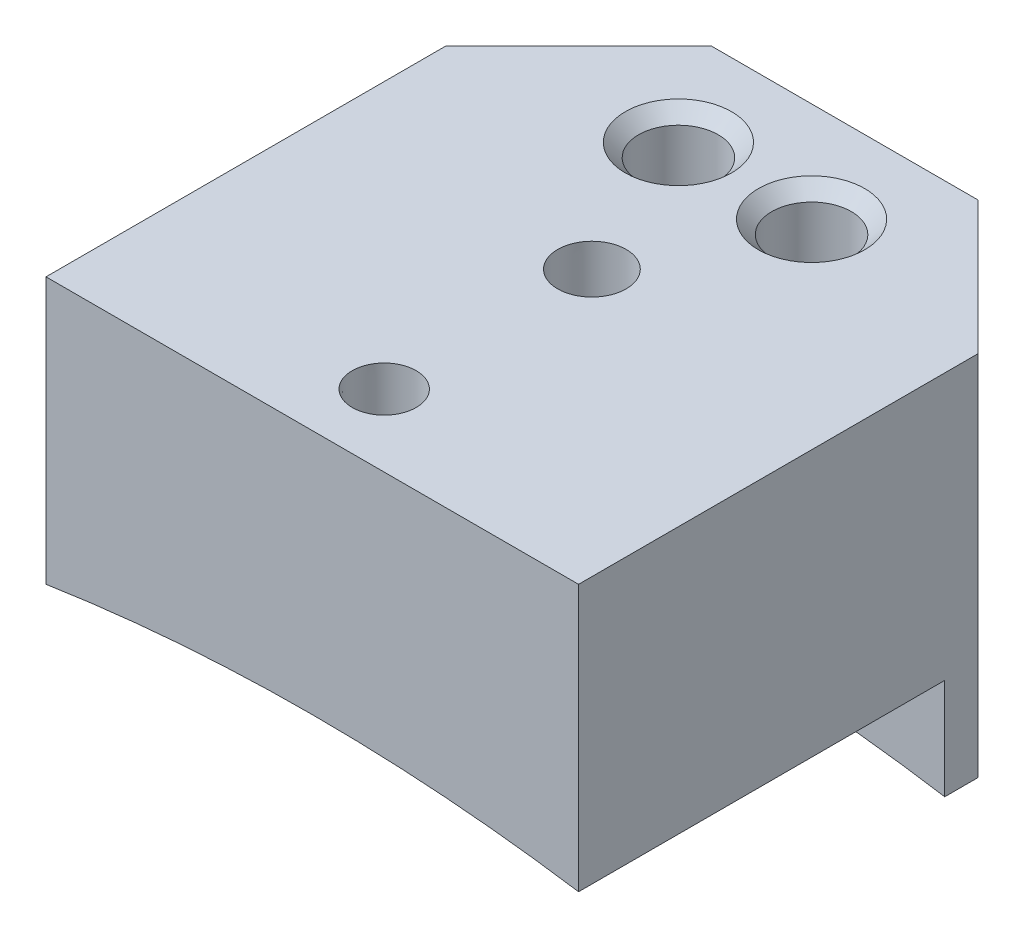
SolidWorks part; units mm, degrees
ref_plane "Front Plane" through (0, 0, 0) normal (0, 0, 1) x (1, 0, 0)
ref_plane "Top Plane" through (0, 0, 0) normal (0, 1, 0) x (1, 0, 0)
ref_plane "Right Plane" through (0, 0, 0) normal (1, 0, 0) x (0, 0, -1)
sketch "Sketch1" plane through (0, 0, 0) normal (0, 1, 0) x (1, 0, 0)
  line L0 (-28.5118, 6.4953) -> (-22.1618, 12.8453)
  line L1 (-22.1618, 12.8453) -> (-9.4618, 12.8453)
  line L2 (-28.5118, 6.4953) -> (-28.5118, -12.5547)
  line L3 (-28.5118, -12.5547) -> (-3.1118, -12.5547)
  line L4 (-3.1118, 6.4953) -> (-3.1118, -12.5547)
  line L5 (-9.4618, 12.8453) -> (-3.1118, 6.4953)
  line L6 (-15.8118, -12.5547) -> (-15.8118, 12.8453) construction
  line L8 (-3.1118, 6.4953) -> (-3.1118, 12.8453) construction
  line L9 (-3.1118, 12.8453) -> (-9.4618, 12.8453) construction
  dimension "D1" = 12.7
  dimension "D2" = 25.4
  dimension "D3" = 25.4
extrude "Boss-Extrude1" add sketch "Sketch1" along normal blind 12.7
sketch "Sketch2" plane through (0, 0, 12.5547) normal (0, 0, 1) x (1, 0, 0)
  circle A0 centre (-15.8118, -82.8523) radius 83.82
  dimension "D1" = 167.64
extrude "Cut-Extrude1" cut sketch "Sketch2" against normal through all both and the other way through all
sketch "Sketch5" plane through (0, 0, -12.8453) normal (0, 0, -1) x (-1, 0, 0)
  line L0 (3.1118, 12.7) -> (3.1118, 0) construction
  line L1 (3.1118, 12.7) -> (3.1118, 0)
  line L4 (28.5118, 12.7) -> (28.5118, 0) construction
  line L5 (28.5118, 12.7) -> (28.5118, 0)
  line L6 (28.5118, -4.8087) -> (28.5118, 0)
  line L7 (3.1118, -4.8087) -> (3.1118, 0)
  line L8 (3.1118, 12.7) -> (28.5118, 12.7)
  arc A0 (3.1118, -4.8087) -> (28.5118, -4.8087) centre (15.8118, -82.8523) cw
  arc A1 (28.5118, 0) -> (3.1118, 0) centre (15.8118, -82.8523) ccw construction
  arc A2 (28.5118, 0) -> (3.1118, 0) centre (15.8118, -82.8523) ccw construction
  dimension "D1" = 79.0702
extrude "Boss-Extrude2" add sketch "Sketch5" against normal blind 7.9375
chamfer "Chamfer1" distance 6.35 angle 45 2 edges at (-28.5118, 3.9457, -12.8453) (-3.1118, 3.9457, -12.8453)
hole_wizard "#10-24 Tapped Hole1" positions "Sketch3" profile "Sketch4" tap size "#10-24" standard "ANSI Inch" end condition through all
sketch "Sketch3" plane through (0, 12.7, 0) normal (0, 1, 0) x (1, 0, 0)
  line L0 (-15.8118, 12.8453) -> (-15.8118, 3.4006) construction
  line L1 (-9.4618, 12.8453) -> (-22.1618, 12.8453) construction
  point P0 (-18.9868, 8.0828)
  point P10 (0, 0)
  point P11 (0, 0)
  point P12 (-12.6368, 8.0828)
  dimension "D1" = 4.7625
  dimension "D2" = 3.175
sketch "Sketch4" plane through (-18.9868, 12.7, -8.0828) normal (1, 0, 0) x (0, 0, 1)
  line L0 (0, 0) -> (0, 17.5087)
  line L1 (0, 17.5087) -> (1.8986, 17.5087)
  line L2 (1.8986, 17.5087) -> (1.8986, 0.635)
  line L3 (1.8986, 0.635) -> (2.5337, 0)
  line L5 (2.5337, 0) -> (0, 0)
  line L6 (-1.8986, 0.635) -> (-2.5337, 0) construction
  line L11 (0, -6.35) -> (0, 107.95) construction
  dimension "Thru Tap Drill Dia." = 3.7973
  dimension "Thru Tap Drill Depth" = 17.5087
  dimension "Near C'Sink Dia." = 5.0673
  dimension "Near C'Sink Angle" = 90
cosmetic thread "Hole Thread3" parameters "D2"=4.826
cosmetic thread "Hole Thread4" parameters "D2"=4.826
sketch "Sketch6" plane through (0, 12.7, 0) normal (0, 1, 0) x (1, 0, 0)
  spline S0 degree 3 poles (-15.9109, -10.6497) (-15.6088, -10.6497) (-15.4088, -10.6093) (-15.0421, -10.4569) (-14.8723, -10.3433) (-14.6614, -10.1321) (-14.5971, -10.0536) (-14.4867, -9.888) (-14.44, -9.8004) (-14.3254, -9.523) (-14.286, -9.3252) (-14.2863, -9.0237) (-14.2962, -8.9248) (-14.3351, -8.7299) (-14.3646, -8.633) (-14.4412, -8.4488) (-14.488, -8.3613) (-14.5989, -8.1955) (-14.6633, -8.1172) (-14.8743, -7.9067) (-15.0444, -7.7932) (-15.4113, -7.6415) (-15.6118, -7.6017) (-15.9102, -7.6018) (-16.0112, -7.6118) (-16.2064, -7.6508) (-16.3014, -7.6796) (-16.5784, -7.7944) (-16.7462, -7.9063) (-16.9595, -8.1198) (-17.0224, -8.1968) (-17.1327, -8.362) (-17.1804, -8.4512) (-17.2567, -8.6357) (-17.2855, -8.7307) (-17.3244, -8.9262) (-17.3342, -9.0271) (-17.3341, -9.3253) (-17.2941, -9.5259) (-17.142, -9.8926) (-17.0285, -10.0627) (-16.8176, -10.2736) (-16.7392, -10.3379) (-16.5735, -10.4485) (-16.486, -10.4953) (-16.3014, -10.5718) (-16.2047, -10.6011) (-16.0099, -10.6398) (-15.9109, -10.6497) (-15.6088, -10.6497) (-15.4088, -10.6093) knots -0.03125 -0.03125 0 0 0.0625 0.0625 0.125 0.125 0.15625 0.15625 0.1875 0.1875 0.25 0.25 0.28125 0.28125 0.3125 0.3125 0.34375 0.34375 0.375 0.375 0.4375 0.4375 0.5 0.5 0.53125 0.53125 0.5625 0.5625 0.625 0.625 0.65625 0.65625 0.6875 0.6875 0.71875 0.71875 0.75 0.75 0.8125 0.8125 0.875 0.875 0.90625 0.90625 0.9375 0.9375 0.96875 0.96875 1 1 1.0625 1.0625 1.125 only from (-15.8102, -10.6497) to (-15.8102, -10.6497) construction
  spline S1 degree 3 poles (-15.9109, -10.6497) (-15.6088, -10.6497) (-15.4088, -10.6093) (-15.0421, -10.4569) (-14.8723, -10.3433) (-14.6614, -10.1321) (-14.5971, -10.0536) (-14.4867, -9.888) (-14.44, -9.8004) (-14.3254, -9.523) (-14.286, -9.3252) (-14.2863, -9.0237) (-14.2962, -8.9248) (-14.3351, -8.7299) (-14.3646, -8.633) (-14.4412, -8.4488) (-14.488, -8.3613) (-14.5989, -8.1955) (-14.6633, -8.1172) (-14.8743, -7.9067) (-15.0444, -7.7932) (-15.4113, -7.6415) (-15.6118, -7.6017) (-15.9102, -7.6018) (-16.0112, -7.6118) (-16.2064, -7.6508) (-16.3014, -7.6796) (-16.5784, -7.7944) (-16.7462, -7.9063) (-16.9595, -8.1198) (-17.0224, -8.1968) (-17.1327, -8.362) (-17.1804, -8.4512) (-17.2567, -8.6357) (-17.2855, -8.7307) (-17.3244, -8.9262) (-17.3342, -9.0271) (-17.3341, -9.3253) (-17.2941, -9.5259) (-17.142, -9.8926) (-17.0285, -10.0627) (-16.8176, -10.2736) (-16.7392, -10.3379) (-16.5735, -10.4485) (-16.486, -10.4953) (-16.3014, -10.5718) (-16.2047, -10.6011) (-16.0099, -10.6398) (-15.9109, -10.6497) (-15.6088, -10.6497) (-15.4088, -10.6093) knots -0.03125 -0.03125 0 0 0.0625 0.0625 0.125 0.125 0.15625 0.15625 0.1875 0.1875 0.25 0.25 0.28125 0.28125 0.3125 0.3125 0.34375 0.34375 0.375 0.375 0.4375 0.4375 0.5 0.5 0.53125 0.53125 0.5625 0.5625 0.625 0.625 0.65625 0.65625 0.6875 0.6875 0.71875 0.71875 0.75 0.75 0.8125 0.8125 0.875 0.875 0.90625 0.90625 0.9375 0.9375 0.96875 0.96875 1 1 1.0625 1.0625 1.125 only from (-15.8102, -10.6497) to (-15.8102, -10.6497)
  spline S2 degree 3 poles (-17.442, 0.8881) (-17.442, 0.5646) (-17.3987, 0.3504) (-17.2355, -0.0422) (-17.1139, -0.2241) (-16.8877, -0.4499) (-16.8036, -0.5187) (-16.6263, -0.6369) (-16.5325, -0.687) (-16.2355, -0.8097) (-16.0236, -0.8519) (-15.7008, -0.8516) (-15.5949, -0.8409) (-15.3862, -0.7993) (-15.2825, -0.7677) (-15.0851, -0.6857) (-14.9915, -0.6355) (-14.814, -0.5168) (-14.7301, -0.4479) (-14.5047, -0.222) (-14.3832, -0.0397) (-14.2207, 0.3532) (-14.178, 0.5678) (-14.1782, 0.8874) (-14.1889, 0.9955) (-14.2306, 1.2046) (-14.2615, 1.3063) (-14.3435, 1.5041) (-14.3946, 1.5994) (-14.5128, 1.7761) (-14.5805, 1.8587) (-14.7329, 2.0109) (-14.8153, 2.0784) (-14.9922, 2.1965) (-15.0878, 2.2476) (-15.2854, 2.3293) (-15.3871, 2.3601) (-15.5964, 2.4017) (-15.7045, 2.4123) (-16.0238, 2.4121) (-16.2385, 2.3692) (-16.6313, 2.2065) (-16.8134, 2.0849) (-17.0392, 1.8591) (-17.1081, 1.7751) (-17.2266, 1.5977) (-17.2767, 1.5039) (-17.3586, 1.3063) (-17.39, 1.2027) (-17.4314, 0.9941) (-17.442, 0.8881) (-17.442, 0.5646) (-17.3987, 0.3504) knots -0.03125 -0.03125 0 0 0.0625 0.0625 0.125 0.125 0.15625 0.15625 0.1875 0.1875 0.25 0.25 0.28125 0.28125 0.3125 0.3125 0.34375 0.34375 0.375 0.375 0.4375 0.4375 0.5 0.5 0.53125 0.53125 0.5625 0.5625 0.59375 0.59375 0.625 0.625 0.65625 0.65625 0.6875 0.6875 0.71875 0.71875 0.75 0.75 0.8125 0.8125 0.875 0.875 0.90625 0.90625 0.9375 0.9375 0.96875 0.96875 1 1 1.0625 1.0625 1.125 only from (-17.442, 0.7803) to (-17.442, 0.7803) construction
  spline S3 degree 3 poles (-17.442, 0.8881) (-17.442, 0.5646) (-17.3987, 0.3504) (-17.2355, -0.0422) (-17.1139, -0.2241) (-16.8877, -0.4499) (-16.8036, -0.5187) (-16.6263, -0.6369) (-16.5325, -0.687) (-16.2355, -0.8097) (-16.0236, -0.8519) (-15.7008, -0.8516) (-15.5949, -0.8409) (-15.3862, -0.7993) (-15.2825, -0.7677) (-15.0851, -0.6857) (-14.9915, -0.6355) (-14.814, -0.5168) (-14.7301, -0.4479) (-14.5047, -0.222) (-14.3832, -0.0397) (-14.2207, 0.3532) (-14.178, 0.5678) (-14.1782, 0.8874) (-14.1889, 0.9955) (-14.2306, 1.2046) (-14.2615, 1.3063) (-14.3435, 1.5041) (-14.3946, 1.5994) (-14.5128, 1.7761) (-14.5805, 1.8587) (-14.7329, 2.0109) (-14.8153, 2.0784) (-14.9922, 2.1965) (-15.0878, 2.2476) (-15.2854, 2.3293) (-15.3871, 2.3601) (-15.5964, 2.4017) (-15.7045, 2.4123) (-16.0238, 2.4121) (-16.2385, 2.3692) (-16.6313, 2.2065) (-16.8134, 2.0849) (-17.0392, 1.8591) (-17.1081, 1.7751) (-17.2266, 1.5977) (-17.2767, 1.5039) (-17.3586, 1.3063) (-17.39, 1.2027) (-17.4314, 0.9941) (-17.442, 0.8881) (-17.442, 0.5646) (-17.3987, 0.3504) knots -0.03125 -0.03125 0 0 0.0625 0.0625 0.125 0.125 0.15625 0.15625 0.1875 0.1875 0.25 0.25 0.28125 0.28125 0.3125 0.3125 0.34375 0.34375 0.375 0.375 0.4375 0.4375 0.5 0.5 0.53125 0.53125 0.5625 0.5625 0.59375 0.59375 0.625 0.625 0.65625 0.65625 0.6875 0.6875 0.71875 0.71875 0.75 0.75 0.8125 0.8125 0.875 0.875 0.90625 0.90625 0.9375 0.9375 0.96875 0.96875 1 1 1.0625 1.0625 1.125 only from (-17.442, 0.7803) to (-17.442, 0.7803)
extrude "Cut-Extrude2" cut sketch "Sketch6" against normal through all
